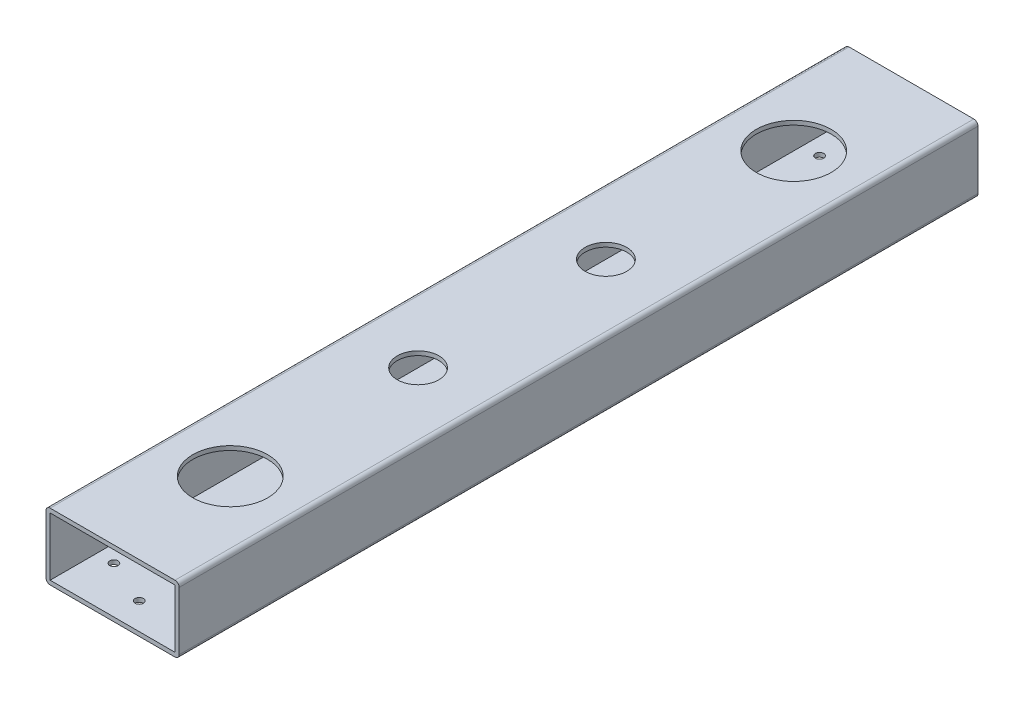
SolidWorks part; units mm, degrees
ref_plane "Front Plane" through (0, 0, 0) normal (0, 0, 1) x (1, 0, 0)
ref_plane "Top Plane" through (0, 0, 0) normal (0, 1, 0) x (1, 0, 0)
ref_plane "Right Plane" through (0, 0, 0) normal (1, 0, 0) x (0, 0, -1)
sketch "Sketch1" plane through (0, 0, 0) normal (0, 0, 1) x (1, 0, 0)
  line L0 (-23.8125, 11.1125) -> (23.8125, 11.1125)
  line L1 (-23.8125, -12.7) -> (23.8125, -12.7)
  line L2 (-25.4, -11.1125) -> (-25.4, 11.1125)
  line L3 (-23.8125, 12.7) -> (23.8125, 12.7)
  line L4 (25.4, -11.1125) -> (25.4, 11.1125)
  line L5 (-25.4, -12.7) -> (25.4, 12.7) construction
  line L6 (-25.4, 12.7) -> (25.4, -12.7) construction
  line L7 (23.8125, -11.1125) -> (23.8125, 11.1125)
  line L8 (-23.8125, -11.1125) -> (23.8125, -11.1125)
  line L9 (-23.8125, -11.1125) -> (-23.8125, 11.1125)
  line L10 (-25.4, -12.7) -> (25.4, -12.7) construction
  line L11 (-25.4, -12.7) -> (-25.4, 12.7) construction
  line L12 (25.4, -12.7) -> (25.4, 12.7) construction
  line L13 (-25.4, 12.7) -> (25.4, 12.7) construction
  arc A0 (-23.8125, -12.7) -> (-25.4, -11.1125) centre (-23.8125, -11.1125) cw
  arc A1 (23.8125, -12.7) -> (25.4, -11.1125) centre (23.8125, -11.1125) ccw
  arc A2 (23.8125, 12.7) -> (25.4, 11.1125) centre (23.8125, 11.1125) cw
  arc A3 (-25.4, 11.1125) -> (-23.8125, 12.7) centre (-23.8125, 11.1125) cw
  point P0 (0, 0)
  dimension "D4" = 1.5875
  dimension "D1" = 25.4
  dimension "D2" = 50.8
  dimension "D3" = 1.5875
extrude "Boss-Extrude1" add sketch "Sketch1" along normal blind 304.8
sketch "Sketch2" plane through (0, 12.7, 0) normal (0, 1, 0) x (1, 0, 0)
  line L0 (0, -259.9) -> (0, -304.8) construction
  line L1 (23.8125, -304.8) -> (-23.8125, -304.8) construction
  line L4 (0, -259.9) -> (0, -44.9) construction
  line L7 (0, -44.9) -> (0, 0) construction
  line L8 (23.8125, 0) -> (-23.8125, 0) construction
  circle A10 centre (0, -259.9) radius 14.2875
  circle A11 centre (0, -44.9) radius 14.2875
  dimension "D1" = 28.575
  dimension "D2" = 28.575
  dimension "D3" = 215
extrude "Cut-Extrude1" cut sketch "Sketch2" against normal up to next and the other way through all
sketch "Sketch3" plane through (0, -12.7, 0) normal (0, -1, 0) x (1, 0, 0)
  circle A0 centre (0, 44.9) radius 12.7
  circle A1 centre (0, 259.9) radius 12.7
  circle A7 centre (0, 259.9) radius 14.2875 construction
  circle A8 centre (0, 44.9) radius 14.2875 construction
  dimension "D1" = 25.4
  dimension "D2" = 25.4
extrude "Cut-Extrude2" cut sketch "Sketch3" against normal up to next and the other way through all
sketch "Sketch6" plane through (0, -12.7, 0) normal (0, -1, 0) x (1, 0, 0)
  line L0 (0, 44.9) -> (0, 259.9) construction
  circle A0 centre (0, 116.5667) radius 3.3782
  circle A2 centre (0, 188.2333) radius 3.3782
  dimension "D3" = 6.7564
  dimension "D1" = 71.6667
  dimension "D2" = 71.6667
extrude "Cut-Extrude5" cut sketch "Sketch6" against normal up to next and the other way through all
sketch "Sketch7" plane through (0, 12.7, 0) normal (0, 1, 0) x (1, 0, 0)
  line L0 (0, -44.9) -> (0, -259.9) construction
  circle A0 centre (0, -116.5667) radius 7.9375
  circle A2 centre (0, -116.5667) radius 3.3782 construction
  circle A4 centre (0, -188.2333) radius 7.9375
  circle A5 centre (0, -188.2333) radius 3.3782 construction
  dimension "D1" = 15.875
extrude "Cut-Extrude6" cut sketch "Sketch7" against normal up to next and the other way through all
sketch "Sketch8" plane through (0, -12.7, 0) normal (0, -1, 0) x (1, 0, 0)
  circle A0 centre (17.272, 287.02) radius 1.5875 construction
  circle A1 centre (0, 294.64) radius 1.5875 construction
  circle A2 centre (-17.272, 287.02) radius 1.5875 construction
  circle A3 centre (17.272, 287.02) radius 1.5875
  circle A4 centre (0, 294.64) radius 1.5875
  circle A5 centre (-17.272, 287.02) radius 1.5875
  circle A6 centre (-17.272, 17.78) radius 1.5875 construction
  circle A7 centre (0, 10.16) radius 1.5875 construction
  circle A8 centre (17.272, 17.78) radius 1.5875 construction
  circle A9 centre (-17.272, 17.78) radius 1.5875
  circle A10 centre (0, 10.16) radius 1.5875
  circle A11 centre (17.272, 17.78) radius 1.5875
extrude "Cut-Extrude7" cut sketch "Sketch8" against normal up to next and the other way through all
